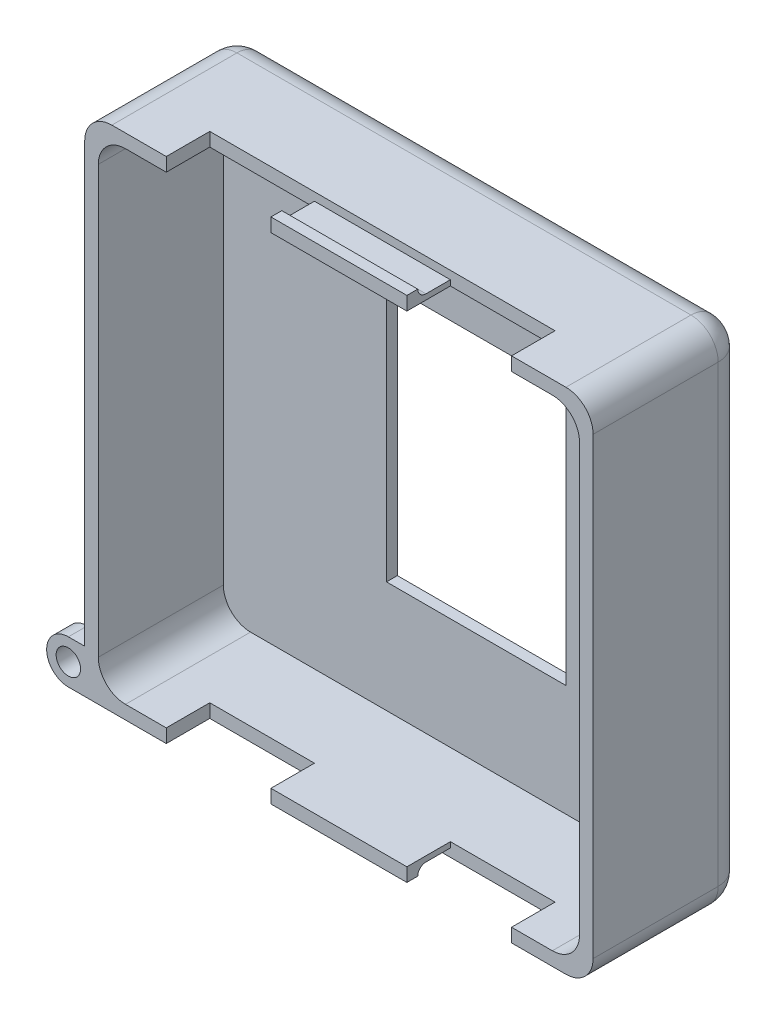
SolidWorks part; units mm, degrees
ref_plane "Front Plane" through (0, 0, 0) normal (0, 0, 1) x (1, 0, 0)
ref_plane "Top Plane" through (0, 0, 0) normal (0, 1, 0) x (1, 0, 0)
ref_plane "Right Plane" through (0, 0, 0) normal (1, 0, 0) x (0, 0, -1)
sketch "Sketch1" plane through (0, 0, 0) normal (0, 0, 1) x (1, 0, 0)
  line L1 (-21.209, -23.749) -> (21.209, -23.749)
  line L2 (-23.749, -21.209) -> (-23.749, 21.209)
  line L3 (-21.209, 23.749) -> (21.209, 23.749)
  line L4 (23.749, -21.209) -> (23.749, 21.209)
  line L5 (-23.749, -23.749) -> (23.749, 23.749) construction
  line L6 (-23.749, 23.749) -> (23.749, -23.749) construction
  arc A0 (-21.209, -23.749) -> (-23.749, -21.209) centre (-21.209, -21.209) cw
  arc A1 (21.209, -23.749) -> (23.749, -21.209) centre (21.209, -21.209) ccw
  arc A2 (21.209, 23.749) -> (23.749, 21.209) centre (21.209, 21.209) cw
  arc A3 (-23.749, 21.209) -> (-21.209, 23.749) centre (-21.209, 21.209) cw
  point P0 (0, 0)
  dimension "D3" = 2.54
  dimension "D1" = 47.498
  dimension "D2" = 47.498
extrude "Boss-Extrude1" add sketch "Sketch1" along normal blind 14.224
sketch "Sketch2" plane through (0, 0, 14.224) normal (0, 0, 1) x (1, 0, 0)
  line L22 (21.209, 23.749) -> (-21.209, 23.749) construction
  line L23 (19.939, -22.479) -> (-19.939, -22.479)
  line L24 (22.479, -19.939) -> (22.479, 19.939)
  line L25 (19.939, 22.479) -> (-19.939, 22.479)
  line L26 (-22.479, -19.939) -> (-22.479, 19.939)
  line L27 (22.479, -22.479) -> (-22.479, 22.479) construction
  line L28 (22.479, 22.479) -> (-22.479, -22.479) construction
  line L29 (-23.749, 21.209) -> (-23.749, -21.209) construction
  arc A14 (-19.939, -22.479) -> (-22.479, -19.939) centre (-19.939, -19.939) cw
  arc A15 (19.939, -22.479) -> (22.479, -19.939) centre (19.939, -19.939) ccw
  arc A16 (22.479, 19.939) -> (19.939, 22.479) centre (19.939, 19.939) ccw
  arc A17 (-19.939, 22.479) -> (-22.479, 19.939) centre (-19.939, 19.939) ccw
  point P12 (0, 0)
  dimension "D3" = 2.54
  dimension "D1" = 1.27
  dimension "D2" = 1.27
extrude "Cut-Extrude1" cut sketch "Sketch2" against normal blind 11.684
fillet "Fillet1" radius 2.54 8 edges at (-23.0051, 23.0051, 0) (0, 23.749, 0) (23.0051, 23.0051, 0) (23.749, 0, 0) (23.0051, -23.0051, 0) (0, -23.749, 0) (-23.0051, -23.0051, 0) (-23.749, 0, 0)
sketch "Sketch3" plane through (0, 23.749, 0) normal (0, 1, 0) x (1, 0, 0)
  line L0 (21.209, -14.224) -> (-21.209, -14.224) construction
  line L1 (16.129, -18.288) -> (-16.129, -18.288)
  line L2 (16.129, -18.288) -> (16.129, -10.16)
  line L3 (16.129, -10.16) -> (-16.129, -10.16)
  line L4 (-16.129, -18.288) -> (-16.129, -10.16)
  line L5 (16.129, -18.288) -> (-16.129, -10.16) construction
  line L6 (16.129, -10.16) -> (-16.129, -18.288) construction
  point P0 (0, -14.224)
  dimension "D1" = 32.258
  dimension "D2" = 4.064
extrude "Cut-Extrude2" cut sketch "Sketch3" against normal through all both and the other way through all
sketch "Sketch4" plane through (23.749, 0, 0) normal (1, 0, 0) x (0, 0, -1)
  line L0 (-14.224, -21.209) -> (-14.224, 21.209) construction
  circle A0 centre (-14.224, -14.986) radius 1.778
  point P4 (-14.224, 0)
  dimension "D2" = 3.556
  dimension "D1" = 14.986
sketch "Sketch5" plane through (0, 0, 0) normal (0, 0, -1) x (-1, 0, 0)
  line L0 (21.209, -21.209) -> (21.209, 21.209) construction
  line L1 (-14.605, 17.145) -> (12.319, 17.145)
  line L2 (-14.605, 17.145) -> (-14.605, -17.145)
  line L3 (-14.605, -17.145) -> (12.319, -17.145)
  line L4 (12.319, 17.145) -> (12.319, -17.145)
  line L5 (-14.605, 17.145) -> (12.319, -17.145) construction
  line L6 (-14.605, -17.145) -> (12.319, 17.145) construction
  point P0 (0, 0)
  dimension "D1" = 26.924
  dimension "D2" = 34.29
  dimension "D3" = 8.89
extrude "Cut-Extrude4" cut sketch "Sketch5" against normal blind 1.524
sketch "Sketch6" plane through (0, 0, 1.524) normal (0, 0, -1) x (-1, 0, 0)
  line L0 (-14.605, 17.145) -> (-14.605, -17.145) construction
  line L1 (-9.525, -12.065) -> (7.239, -12.065)
  line L2 (-9.525, -12.065) -> (-9.525, 12.065)
  line L3 (-9.525, 12.065) -> (7.239, 12.065)
  line L4 (7.239, -12.065) -> (7.239, 12.065)
  line L5 (-9.525, -12.065) -> (7.239, 12.065) construction
  line L6 (-9.525, 12.065) -> (7.239, -12.065) construction
  line L8 (12.319, 17.145) -> (-14.605, 17.145) construction
  line L9 (-14.605, -17.145) -> (12.319, -17.145) construction
  line L10 (12.319, -17.145) -> (12.319, 17.145) construction
  point P0 (0, 0)
  dimension "D1" = 5.08
  dimension "D2" = 5.08
  dimension "D3" = 5.08
  dimension "D4" = 5.08
extrude "Cut-Extrude5" cut sketch "Sketch6" against normal blind 1.524
sketch "Sketch7" plane through (0, 0, 0) normal (0, 0, -1) x (-1, 0, 0)
  line L0 (21.209, 21.209) -> (21.209, -21.209) construction
  line L1 (21.209, 21.209) -> (-21.209, 21.209) construction
  line L2 (-21.209, -21.209) -> (21.209, -21.209) construction
  line L3 (13.589, 21.209) -> (13.589, -21.209) construction
  line L4 (21.209, -21.209) -> (21.209, 21.209) construction
  line L5 (13.589, 17.145) -> (21.209, 17.145) construction
  line L6 (19.939, 17.145) -> (21.209, 17.145)
  line L7 (14.859, 17.145) -> (13.589, 17.145)
  line L8 (21.209, 15.875) -> (16.129, 15.875)
  line L9 (21.209, 10.795) -> (16.129, 10.795)
  line L10 (16.129, 14.605) -> (21.209, 14.605)
  line L11 (21.209, 14.605) -> (21.209, 15.875)
  line L12 (16.129, 12.065) -> (21.209, 12.065)
  line L13 (21.209, 12.065) -> (21.209, 10.795)
  line L14 (13.589, 9.525) -> (21.209, 9.525)
  line L15 (21.209, 9.525) -> (21.209, 5.715)
  line L16 (21.209, 5.715) -> (19.939, 5.715)
  line L17 (19.939, 5.715) -> (19.939, 8.255)
  line L18 (19.939, 8.255) -> (18.034, 8.255)
  line L19 (18.034, 8.255) -> (18.034, 6.985)
  line L20 (18.034, 6.985) -> (16.764, 6.985)
  line L21 (16.764, 6.985) -> (16.764, 8.255)
  line L22 (16.764, 8.255) -> (13.589, 8.255)
  line L23 (13.589, 8.255) -> (13.589, 9.525)
  line L24 (13.589, 4.445) -> (21.209, 4.445)
  line L25 (21.209, 4.445) -> (21.209, 0.635)
  line L26 (21.209, 0.635) -> (19.939, 0.635)
  line L27 (19.939, 0.635) -> (19.939, 3.175)
  line L28 (19.939, 3.175) -> (18.034, 3.175)
  line L29 (18.034, 3.175) -> (18.034, 1.905)
  line L30 (18.034, 1.905) -> (16.764, 1.905)
  line L31 (16.764, 1.905) -> (16.764, 3.175)
  line L32 (16.764, 3.175) -> (13.589, 3.175)
  line L33 (13.589, 3.175) -> (13.589, 4.445)
  line L34 (21.209, -0.635) -> (13.589, -0.635)
  line L35 (13.589, -0.635) -> (13.589, -4.445)
  line L36 (13.589, -4.445) -> (14.859, -4.445)
  line L37 (14.859, -4.445) -> (14.859, -1.905)
  line L38 (14.859, -1.905) -> (21.209, -1.905)
  line L39 (21.209, -1.905) -> (21.209, -0.635)
  line L40 (13.589, -5.715) -> (21.209, -5.715)
  line L41 (21.209, -5.715) -> (21.209, -9.525)
  line L42 (21.209, -9.525) -> (19.939, -9.525)
  line L43 (19.939, -9.525) -> (19.939, -6.985)
  line L44 (19.939, -6.985) -> (18.034, -6.985)
  line L45 (18.034, -6.985) -> (18.034, -8.255)
  line L46 (18.034, -8.255) -> (16.764, -8.255)
  line L47 (16.764, -8.255) -> (16.764, -6.985)
  line L48 (16.764, -6.985) -> (14.859, -6.985)
  line L49 (14.859, -6.985) -> (14.859, -9.525)
  line L50 (14.859, -9.525) -> (13.589, -9.525)
  line L51 (13.589, -9.525) -> (13.589, -5.715)
  line L52 (13.589, -13.0175) -> (21.209, -13.0175) construction
  line L53 (21.209, -13.0175) -> (17.399, -13.0175) construction
  line L54 (17.399, -13.0175) -> (13.589, -13.0175) construction
  line L55 (18.9865, -13.97) -> (18.9865, -15.24)
  line L56 (15.8115, -12.065) -> (15.8115, -10.795)
  line L57 (13.589, -18.7325) -> (21.209, -18.7325) construction
  line L58 (15.8115, -17.78) -> (15.8115, -16.51)
  line L59 (18.9865, -20.955) -> (18.9865, -19.685)
  arc A0 (21.209, 17.145) -> (13.589, 17.145) centre (17.399, 17.145) ccw
  arc A1 (19.939, 17.145) -> (14.859, 17.145) centre (17.399, 17.145) ccw
  arc A2 (16.129, 15.875) -> (16.129, 10.795) centre (16.129, 13.335) ccw
  arc A3 (16.129, 14.605) -> (16.129, 12.065) centre (16.129, 13.335) ccw
  arc A4 (18.9865, -15.24) -> (16.764, -13.0175) centre (18.9865, -13.0175) ccw
  arc A5 (15.8115, -10.795) -> (18.034, -13.0175) centre (15.8115, -13.0175) ccw
  arc A6 (18.9865, -13.97) -> (18.034, -13.0175) centre (18.9865, -13.0175) ccw
  arc A7 (15.8115, -12.065) -> (16.764, -13.0175) centre (15.8115, -13.0175) ccw
  arc A8 (15.8115, -16.51) -> (18.034, -18.7325) centre (15.8115, -18.7325) ccw
  arc A9 (18.9865, -20.955) -> (16.764, -18.7325) centre (18.9865, -18.7325) ccw
  arc A10 (15.8115, -17.78) -> (16.764, -18.7325) centre (15.8115, -18.7325) ccw
  arc A11 (18.9865, -19.685) -> (18.034, -18.7325) centre (18.9865, -18.7325) ccw
  point P15 (13.589, 0)
  dimension "D3" = 5.08
  dimension "D4" = 17.145
  dimension "D5" = 2.54
  dimension "D6" = 5.08
  dimension "D40" = 4.445
  dimension "D41" = 1.27
  dimension "D42" = 1.905
  dimension "D43" = 4.445
  dimension "D44" = 1.27
  dimension "D46" = 1.905
  dimension "D1" = 7.62
  dimension "D2" = 0
  dimension "D7" = 1.27
  dimension "D8" = 1.27
  dimension "D9" = 1.27
  dimension "D10" = 1.27
  dimension "D11" = 1.27
  dimension "D12" = 1.27
  dimension "D13" = 1.905
  dimension "D14" = 1.27
  dimension "D15" = 2.54
  dimension "D16" = 3.81
  dimension "D17" = 1.27
  dimension "D18" = 1.27
  dimension "D19" = 1.27
  dimension "D20" = 1.27
  dimension "D21" = 1.905
  dimension "D22" = 1.27
  dimension "D23" = 2.54
  dimension "D24" = 3.81
  dimension "D25" = 1.27
  dimension "D26" = 1.27
  dimension "D27" = 1.27
  dimension "D28" = 3.81
  dimension "D29" = 1.27
  dimension "D30" = 1.27
  dimension "D31" = 1.27
  dimension "D32" = 1.27
  dimension "D33" = 1.27
  dimension "D34" = 2.54
  dimension "D35" = 2.54
  dimension "D36" = 3.81
  dimension "D37" = 3.81
  dimension "D38" = 1.905
  dimension "D39" = 1.27
sketch "Sketch8" plane through (0, 0, 10.16) normal (0, 0, 1) x (1, 0, 0)
  line L0 (16.129, 22.479) -> (-16.129, 22.479) construction
  line L1 (6.35, 22.987) -> (-6.35, 22.987)
  line L2 (6.35, 22.987) -> (6.35, 22.479)
  line L3 (6.35, 22.479) -> (-6.35, 22.479)
  line L4 (-6.35, 22.987) -> (-6.35, 22.479)
  line L5 (6.35, 22.987) -> (-6.35, 22.479) construction
  line L6 (6.35, 22.479) -> (-6.35, 22.987) construction
  line L7 (-16.129, -22.479) -> (16.129, -22.479) construction
  line L8 (6.35, -22.987) -> (-6.35, -22.987)
  line L9 (6.35, -22.987) -> (6.35, -22.479)
  line L10 (6.35, -22.479) -> (-6.35, -22.479)
  line L11 (-6.35, -22.987) -> (-6.35, -22.479)
  line L12 (6.35, -22.987) -> (-6.35, -22.479) construction
  line L13 (6.35, -22.479) -> (-6.35, -22.987) construction
  point P0 (0, 22.733)
  point P7 (0, -22.733)
  dimension "D1" = 0.508
  dimension "D2" = 12.7
  dimension "D3" = 0
  dimension "D4" = 0.508
  dimension "D5" = 12.7
  dimension "D6" = 0
extrude "Boss-Extrude3" add sketch "Sketch8" along normal blind 4.064
sketch "Sketch9" plane through (0, 22.987, 0) normal (0, 1, 0) x (1, 0, 0)
  line L1 (6.35, -14.224) -> (6.35, -10.16) construction
  line L2 (-6.35, -14.224) -> (6.35, -14.224)
  line L3 (-6.35, -14.224) -> (-6.35, -13.208)
  line L4 (-6.35, -13.208) -> (6.35, -13.208)
  line L5 (6.35, -14.224) -> (6.35, -13.208)
  dimension "D1" = 1.016
extrude "Boss-Extrude4" add sketch "Sketch9" along normal blind 0.762
fillet "Fillet2" radius 0.762 1 edges at (0, 22.987, 13.208)
sketch "Sketch10" plane through (0, -22.987, 0) normal (0, -1, 0) x (1, 0, 0)
  line L0 (-6.35, 14.224) -> (-6.35, 10.16) construction
  line L1 (6.35, 14.224) -> (-6.35, 14.224)
  line L2 (6.35, 14.224) -> (6.35, 13.208)
  line L3 (6.35, 13.208) -> (-6.35, 13.208)
  line L4 (-6.35, 14.224) -> (-6.35, 13.208)
  dimension "D1" = 1.016
extrude "Boss-Extrude5" add sketch "Sketch10" along normal blind 0.762
fillet "Fillet3" radius 0.762 1 edges at (0, -22.987, 13.208)
sketch "Sketch11" plane through (-23.749, 0, 0) normal (-1, 0, 0) x (0, 0, 1)
  line L1 (14.224, -23.749) -> (12.446, -23.749)
  line L2 (14.224, -23.749) -> (14.224, -19.685)
  line L3 (14.224, -19.685) -> (12.446, -19.685)
  line L4 (12.446, -23.749) -> (12.446, -19.685)
  dimension "D1" = 4.064
  dimension "D2" = 1.778
extrude "Boss-Extrude6" add sketch "Sketch11" along normal blind 3.556 and the other way up to body separate body
fillet "Fillet4" 2 edges at (-27.305, -19.685, 13.335) (-27.305, -23.749, 13.335) type full round first side face at (-25.527, -19.685, 13.335) second side face at (-5.461, -23.749, 10.7188) middle face at (-27.305, -21.717, 13.335)
sketch "Sketch12" plane through (0, 0, 12.446) normal (0, 0, -1) x (-1, 0, 0)
  circle A0 centre (25.273, -21.717) radius 1.143
  dimension "D1" = 2.286
extrude "Cut-Extrude7" cut sketch "Sketch12" against normal blind 4.064
extrude "Cut-Extrude8" cut sketch "Sketch7" against normal blind 0.762
